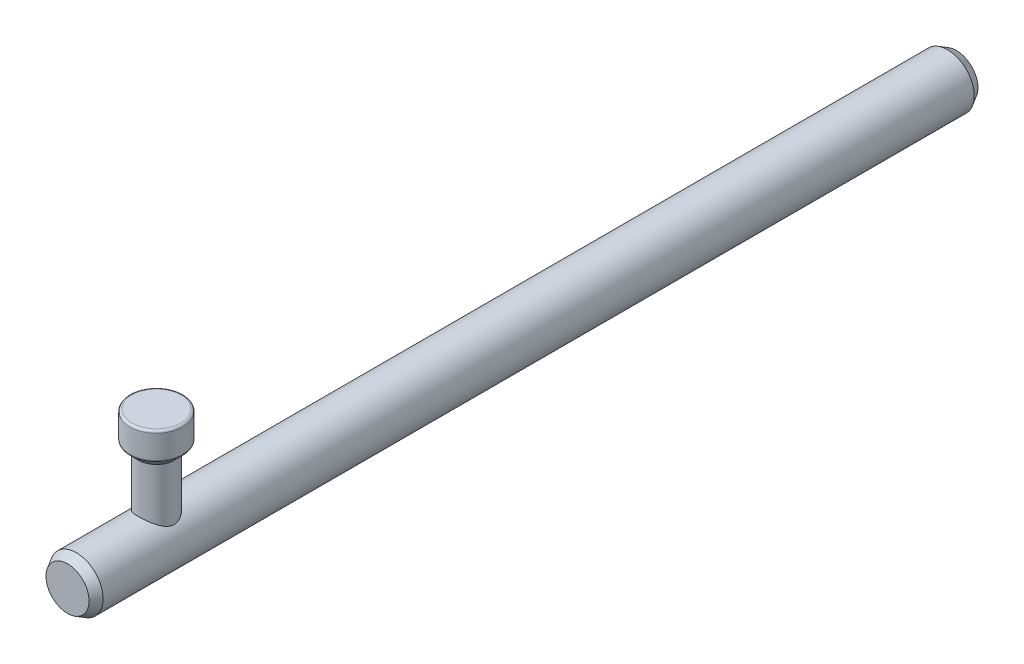
SolidWorks part; units mm, degrees
ref_plane "Front Plane" through (0, 0, 0) normal (0, 0, 1) x (1, 0, 0)
ref_plane "Top Plane" through (0, 0, 0) normal (0, 1, 0) x (1, 0, 0)
ref_plane "Right Plane" through (0, 0, 0) normal (1, 0, 0) x (0, 0, -1)
sketch "Sketch1" plane through (0, 0, 0) normal (0, 0, 1) x (1, 0, 0)
  circle A0 centre (0, 0) radius 6
  dimension "D1" = 12
extrude "Boss-Extrude1" add sketch "Sketch1" along normal blind 50 and the other way blind 150
sketch "Sketch2" plane through (0, 0, 0) normal (0, 1, 0) x (1, 0, 0)
  line L0 (-6.6, 0) -> (6.6, 0) construction
  line L1 (0, -6.6) -> (0, 6.6) construction
  circle A0 centre (0, -30) radius 4
  dimension "D1" = 8
  dimension "D2" = 30
extrude "Boss-Extrude2" add sketch "Sketch2" along normal blind 25
sketch "Sketch3" plane through (0, 25, 0) normal (0, 1, 0) x (1, 0, 0)
  circle A0 centre (0, -30) radius 6
  circle A1 centre (0, -30) radius 4 construction
  dimension "D1" = 12
extrude "Boss-Extrude3" add sketch "Sketch3" against normal blind 8
chamfer "Chamfer1" distance 2 angle 30 2 edges at (6, 0, 50) (6, 0, -150) first distance on face at (6, 0, 50)
chamfer "Chamfer2" distance 2 angle 45 1 edges at (0, 17, 36)
fillet "Fillet1" radius 0.5 2 edges at (0, 25, 36) (0, 19, 36)
